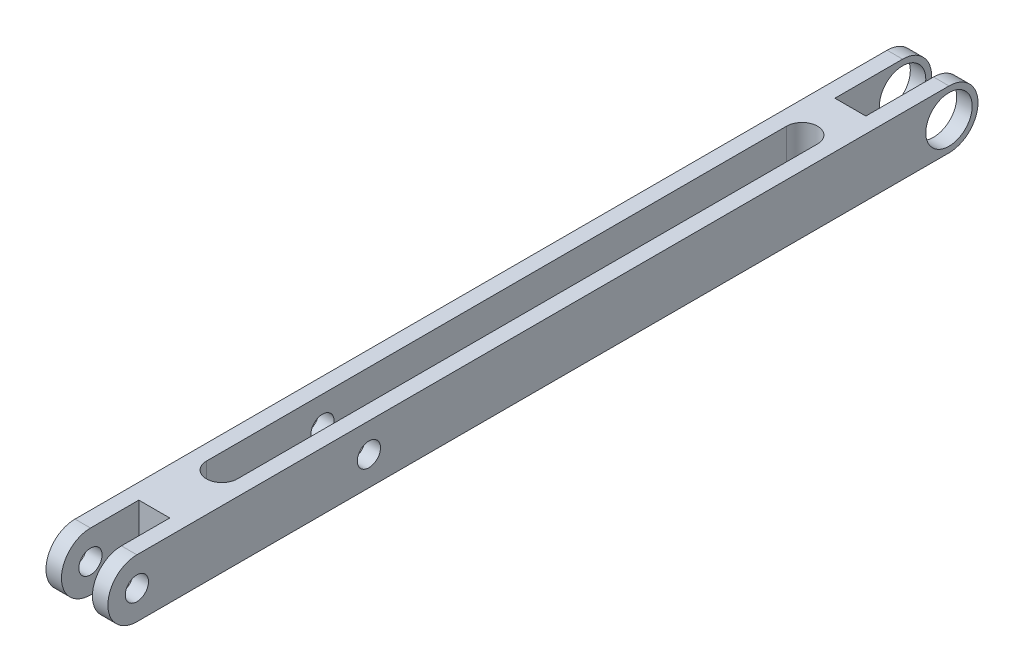
SolidWorks part; units mm, degrees
material "ABS"
ref_plane "前视基准面" through (0, 0, 0) normal (0, 0, 1) x (1, 0, 0)
ref_plane "上视基准面" through (0, 0, 0) normal (0, 1, 0) x (1, 0, 0)
ref_plane "右视基准面" through (0, 0, 0) normal (1, 0, 0) x (0, 0, -1)
sketch "草图2" plane through (0, 0, 0) normal (1, 0, 0) x (0, 0, -1)
  line L0 (-105, 7.5) -> (-105, -7.5) construction
  line L1 (-105, -7.5) -> (105, -7.5)
  line L3 (-105, 7.5) -> (105, 7.5)
  line L5 (-105, -7.5) -> (105, 7.5) construction
  line L6 (-105, 7.5) -> (105, -7.5) construction
  line L7 (105, 7.5) -> (105, -7.5) construction
  arc A0 (-105, 7.5) -> (-105, -7.5) centre (-105, 0) ccw
  arc A1 (105, 7.5) -> (105, -7.5) centre (105, 0) cw
  point P0 (0, 0)
  dimension "D1" = 15
  dimension "D2" = 210
extrude "凸台-拉伸1" add sketch "草图2" along normal blind 16
sketch "草图3" plane through (0, 7.5, 0) normal (0, 1, 0) x (1, 0, 0)
  line L1 (4, -112.5) -> (4, -92.5)
  line L2 (0, -112.5) -> (16, -112.5) construction
  line L3 (4, -92.5) -> (12, -92.5)
  line L4 (12, -92.5) -> (12, -112.5)
  line L5 (12, -112.5) -> (4, -112.5)
  line L6 (0, 105) -> (0, -105) construction
  line L7 (16, 105) -> (16, -105) construction
  line L10 (4, 112.5) -> (12, 112.5)
  line L14 (4, 112.5) -> (4, 87.5)
  line L15 (4, 87.5) -> (12, 87.5)
  line L16 (12, 87.5) -> (12, 112.5)
  line L17 (16, 105) -> (0, 105) construction
  dimension "D1" = 4
  dimension "D2" = 4
  dimension "D3" = 20
  dimension "D4" = 8
  dimension "D5" = 25
  dimension "D6" = 7.5
  dimension "D7" = 4
extrude "切除-拉伸1" cut sketch "草图3" against normal through all
sketch "草图4" plane through (16, 0, 0) normal (1, 0, 0) x (0, 0, -1)
  circle A0 centre (-105, 0) radius 3
  circle A1 centre (105, 0) radius 6
  dimension "D1" = 6
  dimension "D2" = 12
extrude "切除-拉伸2" cut sketch "草图4" against normal through all
sketch "草图5" plane through (0, -7.5, 0) normal (0, -1, 0) x (1, 0, 0)
  line L0 (8, 75) -> (8, -75) construction
  line L1 (12, 75) -> (12, -75)
  line L2 (4, 75) -> (4, -75)
  line L3 (0, 0) -> (8, 0) construction
  line L4 (0, 105) -> (0, -105) construction
  arc A0 (12, 75) -> (4, 75) centre (8, 75) ccw
  arc A1 (4, -75) -> (12, -75) centre (8, -75) ccw
  point P2 (8, 0)
  dimension "D1" = 8
  dimension "D2" = 8
  dimension "D3" = 150
extrude "切除-拉伸3" cut sketch "草图5" against normal through all
sketch "草图6" plane through (0, 0, 0) normal (-1, 0, 0) x (0, 0, 1)
  line L0 (45, 0) -> (0, 0) construction
  circle A1 centre (45, 0) radius 3
  circle A3 centre (105, 0) radius 3 construction
  dimension "D1" = 60
  dimension "D2" = 6
extrude "切除-拉伸4" cut sketch "草图6" against normal through all
